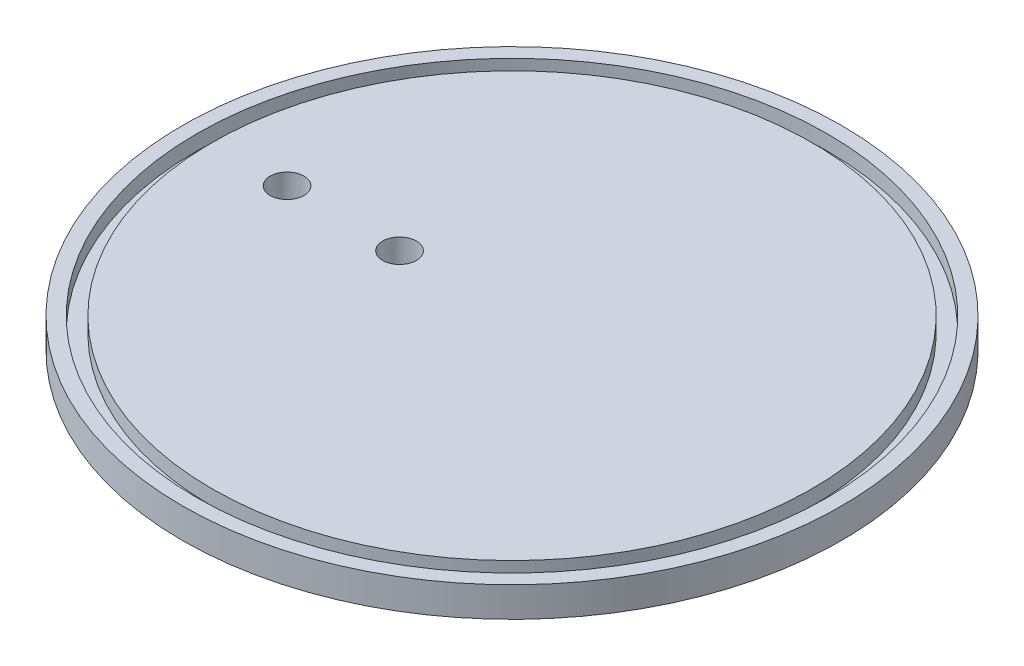
SolidWorks part; units mm, degrees
ref_plane "Front Plane" through (0, 0, 0) normal (0, 0, 1) x (1, 0, 0)
ref_plane "Top Plane" through (0, 0, 0) normal (0, 1, 0) x (1, 0, 0)
ref_plane "Right Plane" through (0, 0, 0) normal (1, 0, 0) x (0, 0, -1)
sketch "Sketch2" plane through (0, 0, 0) normal (0, 0, 1) x (1, 0, 0)
  line L0 (-40, 0) -> (-60, 100) construction
  line L1 (-60, 100) -> (0, 100) construction
  line L2 (0, 100) -> (0, 0) construction
  line L3 (0, 0) -> (-40, 0) construction
  line L4 (-41.6396, -2) -> (-62.4396, 102) construction
  line L5 (-62.4396, 102) -> (2, 102) construction
  line L6 (2, 102) -> (2, -2) construction
  line L8 (-42.0396, 0) -> (-43.9517, 0)
  line L9 (-40, 0) -> (-40, -2)
  line L10 (-42.0396, 0) -> (-42.0396, -2)
  line L12 (-40, 0) -> (0, 0)
  line L14 (-40, -2) -> (-42.0396, -2)
  line L17 (-40, -2) -> (-41.6396, -2) construction
  line L20 (-34.0168, -4) -> (0, -4)
  line L21 (0, 0) -> (0, -4)
  line L22 (2, -2) -> (-41.6396, -2) construction
  line L23 (-40, 0) -> (0, 0)
  line L24 (-43.9517, 0) -> (-43.9517, -4)
  line L25 (-43.9517, -4) -> (-34.0168, -4)
  dimension "D1" = 100
  dimension "D2" = 60
  dimension "D3" = 40
  dimension "D5" = 1.9121
  dimension "D4" = 2
revolve "Revolve1" add sketch "Sketch2" angle 360 about L2 region at (-21.5235, -2.0238, 0)
sketch "Sketch3" plane through (0, 0, 0) normal (0, 0, 1) x (1, 0, 0)
  line L2 (5, -4) -> (-35, -4)
  line L3 (5, -4) -> (5, -9)
  line L4 (5, -9) -> (-35, -9)
  line L7 (-35, -4) -> (-35, -9)
  ellipse E0 centre (5, -15.35) end of major axis (20, -15.35) minor radius 11.35
  dimension "D1" = 5
  dimension "D2" = 40
  dimension "D3" = 5
extrude "Boss-Extrude1" add sketch "Sketch3" along normal blind 10 and the other way blind 10 contours E0 L2 L7 L4 region at (-19.2388, -6.3723, 0)
sketch "Sketch4" plane through (0, -9, 0) normal (0, -1, 0) x (1, 0, 0)
  line L0 (-35, -10) -> (-35, 10) construction
  circle A0 centre (-30, 0) radius 2.25
  circle A1 centre (-15, 0) radius 2.25
  dimension "D1" = 5
  dimension "D2" = 15
extrude "Cut-Extrude1" cut sketch "Sketch4" against normal blind 16
